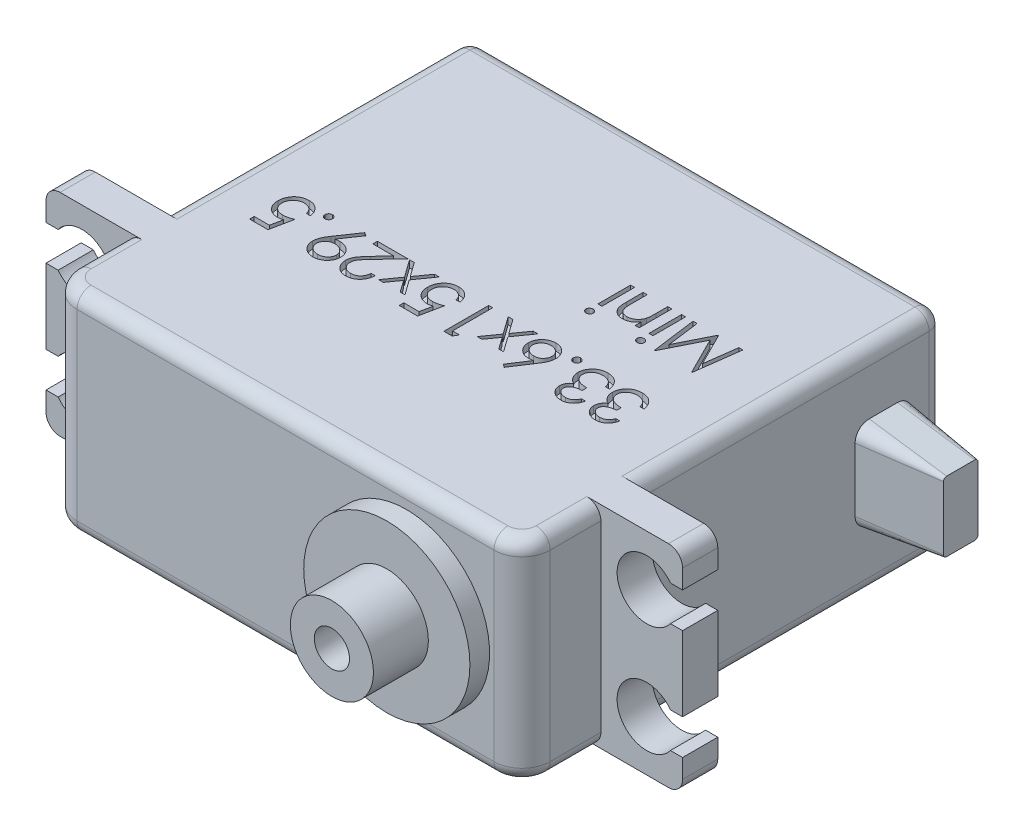
SolidWorks part; units mm, degrees
ref_plane "Front" through (0, 0, 0) normal (0, 0, 1) x (1, 0, 0)
ref_plane "Top" through (0, 0, 0) normal (0, 1, 0) x (1, 0, 0)
ref_plane "Right" through (0, 0, 0) normal (1, 0, 0) x (0, 0, -1)
sketch "Sketch1" plane through (0, 0, 0) normal (0, 0, 1) x (1, 0, 0)
  line L1 (-16.8, -7.5) -> (16.8, -7.5)
  line L2 (-16.8, -7.5) -> (-16.8, 7.5)
  line L3 (-16.8, 7.5) -> (16.8, 7.5)
  line L4 (16.8, -7.5) -> (16.8, 7.5)
  line L5 (-16.8, -7.5) -> (16.8, 7.5) construction
  line L6 (-16.8, 7.5) -> (16.8, -7.5) construction
  point P0 (0, 0)
  dimension "D1" = 15
  dimension "D2" = 33.6
extrude "Boss-Extrude1" add sketch "Sketch1" along normal mid plane 29.9
sketch "Sketch2" plane through (0, 0, 0) normal (0, 1, 0) x (1, 0, 0)
  line L1 (-22.6, -9.35) -> (22.6, -9.35)
  line L2 (-22.6, -9.35) -> (-22.6, -6.85)
  line L3 (-22.6, -6.85) -> (22.6, -6.85)
  line L4 (22.6, -9.35) -> (22.6, -6.85)
  line L5 (-22.6, -9.35) -> (22.6, -6.85) construction
  line L6 (-22.6, -6.85) -> (22.6, -9.35) construction
  line L8 (16.8, 14.95) -> (-16.8, 14.95) construction
  point P0 (0, -8.1)
  dimension "D1" = 2.5
  dimension "D2" = 45.2
  dimension "D3" = 21.8
extrude "Boss-Extrude2" add sketch "Sketch2" along normal up to vertex (7.5 mm away) and the other way up to vertex (7.5 mm away) up to point (-16.8, 7.5, 14.95) other way up to point (-16.8, -7.5, -14.95)
sketch "Sketch6" plane through (0, 0, 9.35) normal (0, 0, 1) x (1, 0, 0)
  line L0 (0, 7.5) -> (0, -7.5) construction
  line L1 (16.8, 7.5) -> (-16.8, 7.5) construction
  line L2 (-16.8, -7.5) -> (16.8, -7.5) construction
  line L3 (-22.6, 5.15) -> (-21.7375, 5.15)
  line L4 (22.6, 7.5) -> (22.6, -7.5) construction
  line L5 (22.6, 0) -> (-22.6, 0) construction
  line L6 (-22.6, 7.5) -> (-22.6, -7.5) construction
  line L7 (-22.6, 2.65) -> (-21.7375, 2.65)
  line L8 (-20.05, 3.9) -> (-21.6411, 3.9) construction
  line L9 (-22.6, 5.15) -> (-22.6, 2.65)
  line L10 (22.6, 2.65) -> (21.7375, 2.65)
  line L11 (22.6, 5.15) -> (22.6, 2.65)
  line L12 (22.6, 5.15) -> (21.7375, 5.15)
  line L13 (22.6, -2.65) -> (21.7375, -2.65)
  line L14 (22.6, -5.15) -> (22.6, -2.65)
  line L15 (22.6, -5.15) -> (21.7375, -5.15)
  line L16 (-22.6, -2.65) -> (-21.7375, -2.65)
  line L17 (-22.6, -5.15) -> (-22.6, -2.65)
  line L18 (-22.6, -5.15) -> (-21.7375, -5.15)
  arc A0 (-21.7375, 2.65) -> (-21.7375, 5.15) centre (-20.05, 3.9) ccw
  arc A1 (21.7375, 2.65) -> (21.7375, 5.15) centre (20.05, 3.9) cw
  arc A2 (21.7375, -2.65) -> (21.7375, -5.15) centre (20.05, -3.9) ccw
  arc A3 (-21.7375, -2.65) -> (-21.7375, -5.15) centre (-20.05, -3.9) cw
  dimension "D3" = 4.2
  dimension "D1" = 40.1
  dimension "D2" = 7.8
  dimension "D4" = 2.5
extrude "Cut-Extrude2" cut sketch "Sketch6" against normal blind 10
sketch "Sketch3" plane through (0, 0, 14.95) normal (0, 0, 1) x (1, 0, 0)
  line L0 (22.6, 2.65) -> (22.6, -2.65) construction
  circle A0 centre (8.6, 0) radius 2.95
  dimension "D2" = 5.9
  dimension "D1" = 14
extrude "Boss-Extrude3" add sketch "Sketch3" along normal blind 5.3
sketch "Sketch4" plane through (0, 7.5, 0) normal (0, -1, 0) x (1, 0, 0)
  text T0 "33.6x15x29.5\r\nMini" font "Century Gothic" height in points 12
extrude "Cut-Extrude1" cut sketch "Sketch4" along normal blind 0.5
sketch "Sketch5" [suppressed] plane through (0, 0, 16.95) normal (0, 0, 1) x (1, 0, 0)
  circle A0 centre (10.5356, 0) radius 10
  dimension "D1" = 20
ref_axis "Axis1" [suppressed] through (10.5356, 0, 16.95) along (0, 0, -1)
sketch "Sketch7" plane through (0, 0, 14.95) normal (0, 0, 1) x (1, 0, 0)
  circle A0 centre (8.6, 0) radius 5.9
  dimension "D1" = 11.8
extrude "Boss-Extrude4" add sketch "Sketch7" along normal blind 1.4
fillet "Fillet1" radius 2 2 edges at (-16.8, 0, 14.95) (16.8, 0, 14.95)
sketch "Sketch8" plane through (16.8, 0, 0) normal (1, 0, 0) x (0, 0, -1)
  line L0 (14.95, -7.5) -> (14.95, 7.5) construction
  line L1 (9.7, 3.25) -> (11.7, 3.25)
  line L2 (8.7, 2.25) -> (8.7, -2.25)
  line L3 (9.7, -3.25) -> (11.7, -3.25)
  line L4 (12.7, 2.25) -> (12.7, -2.25)
  arc A0 (11.7, -3.25) -> (12.7, -2.25) centre (11.7, -2.25) ccw
  arc A1 (8.7, -2.25) -> (9.7, -3.25) centre (9.7, -2.25) ccw
  arc A2 (9.7, 3.25) -> (8.7, 2.25) centre (9.7, 2.25) ccw
  arc A3 (11.7, 3.25) -> (12.7, 2.25) centre (11.7, 2.25) cw
  point P4 (8.7, 0)
  point P10 (12.7, -3.25)
  point P15 (8.7, 3.25)
  point P18 (12.7, 3.25)
  dimension "D4" = 1
  dimension "D5" = 1
  dimension "D1" = 4
  dimension "D2" = 6.5
  dimension "D3" = 2.25
extrude "Boss-Extrude5" add sketch "Sketch8" along normal blind 5.5 draft 8
sketch "Sketch10" plane through (0, -7.5, 0) normal (0, -1, 0) x (1, 0, 0)
  line L12 (14.8, 14.95) -> (-14.8, 14.95)
  line L13 (-16.8, 12.95) -> (-16.8, 9.35)
  line L14 (-16.8, 9.35) -> (-22.6, 9.35)
  line L15 (-22.6, 9.35) -> (-22.6, 6.85)
  line L16 (-22.6, 6.85) -> (-16.8, 6.85)
  line L17 (-16.8, 6.85) -> (-16.8, -14.95)
  line L18 (-16.8, -14.95) -> (16.8, -14.95)
  line L19 (16.8, -14.95) -> (16.8, 6.85)
  line L20 (16.8, 6.85) -> (22.6, 6.85)
  line L21 (22.6, 6.85) -> (22.6, 9.35)
  line L22 (22.6, 9.35) -> (16.8, 9.35)
  line L23 (16.8, 9.35) -> (16.8, 12.95)
  line L24 (14.8, 14.95) -> (-14.8, 14.95)
  line L25 (-16.8, 12.95) -> (-16.8, 9.35)
  line L26 (-16.8, 9.35) -> (-22.6, 9.35)
  line L27 (-22.6, 9.35) -> (-22.6, 6.85)
  line L28 (-22.6, 6.85) -> (-16.8, 6.85)
  line L29 (-16.8, 6.85) -> (-16.8, -14.95)
  line L30 (-16.8, -14.95) -> (16.8, -14.95)
  line L31 (16.8, -14.95) -> (16.8, 6.85)
  line L32 (16.8, 6.85) -> (22.6, 6.85)
  line L33 (22.6, 6.85) -> (22.6, 9.35)
  line L34 (22.6, 9.35) -> (16.8, 9.35)
  line L35 (16.8, 9.35) -> (16.8, 12.95)
  arc A2 (-14.8, 14.95) -> (-16.8, 12.95) centre (-14.8, 12.95) ccw
  arc A3 (16.8, 12.95) -> (14.8, 14.95) centre (14.8, 12.95) ccw
  arc A4 (-14.8, 14.95) -> (-16.8, 12.95) centre (-14.8, 12.95) ccw
  arc A5 (16.8, 12.95) -> (14.8, 14.95) centre (14.8, 12.95) ccw
  dimension "D1" = 0
fillet "Fillet2" radius 1 18 edges at (-16.8, -7.5, 11.15) (-16.2142, -7.5, 14.3642) (16.8, -7.5, 11.15) (16.2142, -7.5, 14.3642) (-16.8, 7.5, 11.15) (-16.2142, 7.5, 14.3642) (0, 7.5, 14.95) (16.2142, 7.5, 14.3642) (0, -7.5, 14.95) (16.8, 7.5, 11.15) (16.8, 7.5, -4.05) (16.8, 0, -14.95) (0, 7.5, -14.95) (-16.8, 7.5, -4.05) (-16.8, 0, -14.95) (0, -7.5, -14.95) (-16.8, -7.5, -4.05) (16.8, -7.5, -4.05)
fillet "Fillet3" radius 1 4 edges at (22.6, 7.5, 8.1) (-22.6, 7.5, 8.1) (22.6, -7.5, 8.1) (-22.6, -7.5, 8.1)
sketch "Sketch9" plane through (0, 0, 20.25) normal (0, 0, 1) x (1, 0, 0)
  circle A0 centre (8.6, 0) radius 1.25
  dimension "D1" = 2.5
extrude "Cut-Extrude3" cut sketch "Sketch9" against normal blind 3
sketch "Sketch11" [suppressed] plane through (0, 0, 9.35) normal (0, 0, 1) x (1, 0, 0)
  line L0 (22.6, -0.6147) -> (16.8, 1.8091)
  line L10 (22.6, 5.15) -> (22.6, 6.5)
  line L11 (21.6, 7.5) -> (15.8, 7.5)
  line L12 (16.8, 6.5) -> (16.8, -6.5)
  line L13 (15.8, -7.5) -> (21.6, -7.5)
  line L14 (22.6, -6.5) -> (22.6, -5.15)
  line L15 (22.6, -5.15) -> (21.7375, -5.15)
  line L16 (21.7375, -2.65) -> (22.6, -2.65)
  line L17 (22.6, -2.65) -> (22.6, 2.65)
  line L18 (22.6, 2.65) -> (21.7375, 2.65)
  line L19 (21.7375, 5.15) -> (22.6, 5.15)
  line L20 (22.6, 5.15) -> (22.6, 6.5)
  line L21 (21.6, 7.5) -> (15.8, 7.5)
  line L22 (16.8, 6.5) -> (16.8, 1.8091)
  line L27 (22.6, -0.6147) -> (22.6, 2.65)
  line L28 (22.6, 2.65) -> (21.7375, 2.65)
  line L29 (21.7375, 5.15) -> (22.6, 5.15)
  arc A6 (22.6, 6.5) -> (21.6, 7.5) centre (21.6, 6.5) ccw
  arc A7 (16.8, 6.5) -> (15.8, 7.5) centre (15.8, 6.5) ccw
  arc A8 (15.8, -7.5) -> (16.8, -6.5) centre (15.8, -6.5) ccw
  arc A9 (21.6, -7.5) -> (22.6, -6.5) centre (21.6, -6.5) ccw
  arc A10 (21.7375, -2.65) -> (21.7375, -5.15) centre (20.05, -3.9) ccw
  arc A11 (21.7375, 5.15) -> (21.7375, 2.65) centre (20.05, 3.9) ccw
  arc A12 (22.6, 6.5) -> (21.6, 7.5) centre (21.6, 6.5) ccw
  arc A13 (16.8, 6.5) -> (15.8, 7.5) centre (15.8, 6.5) ccw
  arc A17 (21.7375, 5.15) -> (21.7375, 2.65) centre (20.05, 3.9) ccw
  dimension "D1" = 0
extrude "Cut-Extrude4" [suppressed] cut sketch "Sketch11" against normal blind 3
